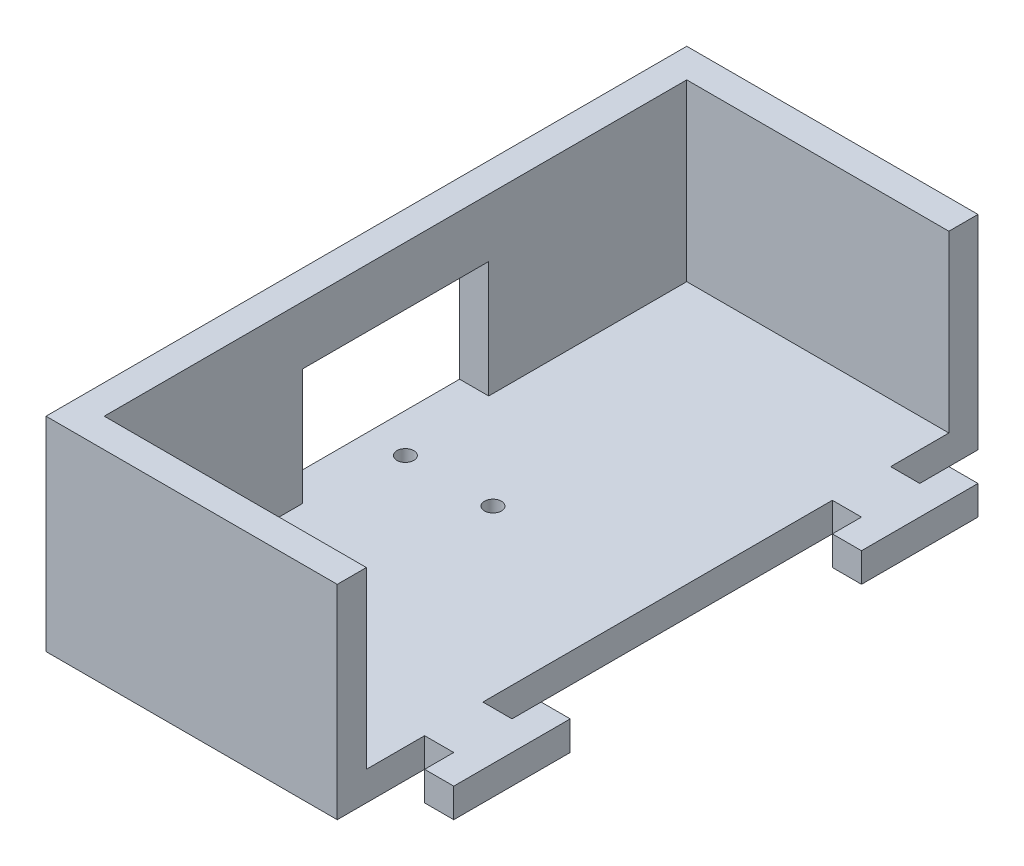
SolidWorks part; units mm, degrees
ref_plane "Front Plane" through (0, 0, 0) normal (0, 0, 1) x (1, 0, 0)
ref_plane "Top Plane" through (0, 0, 0) normal (0, 1, 0) x (1, 0, 0)
ref_plane "Right Plane" through (0, 0, 0) normal (1, 0, 0) x (0, 0, -1)
sketch "Sketch1" plane through (0, 0, 0) normal (0, 1, 0) x (1, 0, 0)
  line L1 (-38.1, -69.85) -> (25.4, -69.85)
  line L2 (-38.1, -69.85) -> (-38.1, 69.85)
  line L3 (-38.1, 69.85) -> (25.4, 69.85)
  line L4 (25.4, -69.85) -> (25.4, 69.85)
  line L5 (-38.1, -69.85) -> (25.4, 69.85) construction
  line L6 (-38.1, 69.85) -> (25.4, -69.85) construction
  point P0 (-6.35, 0)
  dimension "D1" = 63.5
  dimension "D2" = 139.7
  dimension "D3" = 6.35
extrude "Boss-Extrude1" add sketch "Sketch1" along normal blind 6.35
sketch "Sketch3" plane through (0, 6.35, 0) normal (0, 1, 0) x (1, 0, 0)
  line L0 (25.4, -69.85) -> (25.4, 69.85) construction
  line L1 (-38.1, 69.85) -> (25.4, 69.85)
  line L2 (-38.1, 69.85) -> (-38.1, 63.5)
  line L3 (-38.1, 63.5) -> (25.4, 63.5)
  line L4 (25.4, 69.85) -> (25.4, 63.5)
  line L6 (-38.1, -69.85) -> (25.4, -69.85)
  line L7 (-38.1, -69.85) -> (-38.1, -63.5)
  line L8 (-38.1, -63.5) -> (25.4, -63.5)
  line L9 (25.4, -69.85) -> (25.4, -63.5)
  dimension "D1" = 6.35
extrude "Boss-Extrude2" add sketch "Sketch3" along normal blind 38.1
sketch "Sketch6" plane through (0, 6.35, 0) normal (0, 1, 0) x (1, 0, 0)
  line L0 (25.4, -63.5) -> (25.4, 63.5) construction
  line L1 (25.4, 50.8) -> (31.75, 50.8)
  line L2 (25.4, 50.8) -> (25.4, 38.1)
  line L3 (25.4, 38.1) -> (31.75, 38.1)
  line L5 (25.4, 69.85) -> (-38.1, 69.85) construction
  line L6 (31.75, 57.15) -> (38.1, 57.15)
  line L7 (31.75, 57.15) -> (31.75, 50.8)
  line L8 (31.75, 31.75) -> (38.1, 31.75)
  line L9 (38.1, 57.15) -> (38.1, 31.75)
  line L10 (31.75, 38.1) -> (31.75, 31.75)
  point P10 (38.1, 44.45)
  point P11 (25.4, 44.45)
  dimension "D1" = 6.35
  dimension "D2" = 12.7
  dimension "D3" = 25.4
  dimension "D4" = 6.35
  dimension "D5" = 25.4
extrude "Boss-Extrude3" add sketch "Sketch6" against normal up to surface (6.35 mm away) up to face at (-6.35, 0, 0)
mirror "Mirror1" about plane through (0, 0, 0) normal (0, 0, 1) of "Boss-Extrude3"
sketch "Sketch7" plane through (0, 0, 0) normal (0, -1, 0) x (1, 0, 0)
  circle A0 centre (-10.5, 0) radius 1.85 construction
  circle A1 centre (-29.6, 0) radius 1.85 construction
  circle A2 centre (-10.5, 0) radius 1.85
  circle A3 centre (-29.6, 0) radius 1.85
extrude "Cut-Extrude1" cut sketch "Sketch7" against normal through all
sketch "Sketch8" plane through (0, 6.35, 0) normal (0, 1, 0) x (1, 0, 0)
  line L0 (-38.1, 69.85) -> (-38.1, 63.5) construction
  line L1 (-38.1, 63.5) -> (-31.75, 63.5)
  line L2 (-38.1, 63.5) -> (-38.1, 20.32)
  line L3 (-38.1, 20.32) -> (-31.75, 20.32)
  line L4 (-31.75, 63.5) -> (-31.75, 20.32)
  line L5 (-38.1, -63.5) -> (-31.75, -63.5)
  line L6 (-38.1, -63.5) -> (-38.1, -20.32)
  line L7 (-38.1, -20.32) -> (-31.75, -20.32)
  line L8 (-31.75, -63.5) -> (-31.75, -20.32)
  dimension "D1" = 40.64
extrude "Boss-Extrude4" add sketch "Sketch8" along normal up to surface (38.1 mm away) up to face at (-6.35, 44.45, 66.675)
sketch "Sketch9" plane through (-38.1, 0, 0) normal (-1, 0, 0) x (0, 0, 1)
  line L0 (20.32, 44.45) -> (20.32, 6.35) construction
  line L1 (-20.32, 44.45) -> (20.32, 44.45)
  line L2 (-20.32, 44.45) -> (-20.32, 31.75)
  line L3 (-20.32, 31.75) -> (20.32, 31.75)
  line L4 (20.32, 44.45) -> (20.32, 31.75)
  line L5 (-20.32, 6.35) -> (20.32, 6.35) construction
  dimension "D1" = 25.4
extrude "Boss-Extrude5" add sketch "Sketch9" against normal up to surface (6.35 mm away) up to face at (-31.75, 25.4, 41.91)
